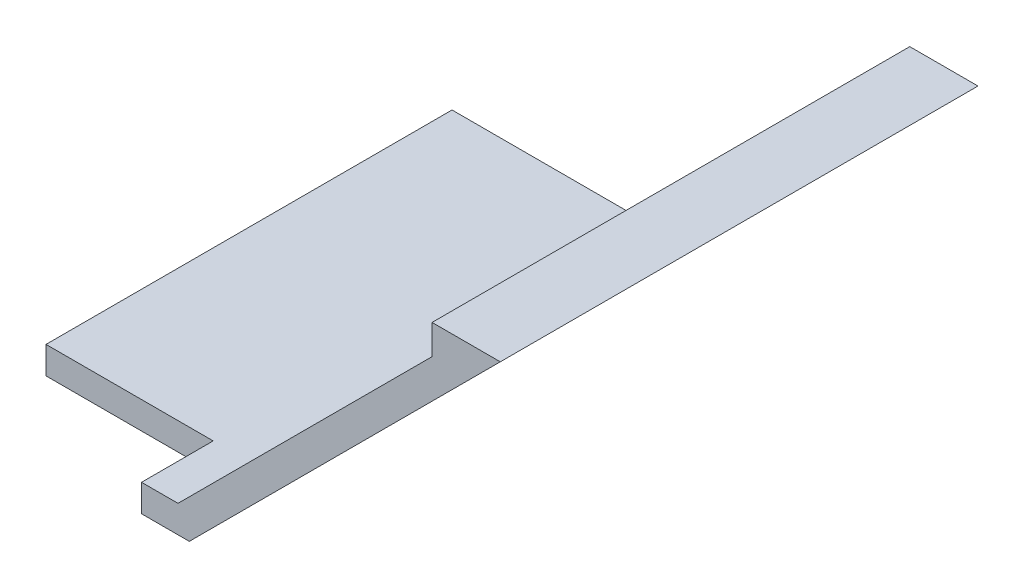
SolidWorks part; units mm, degrees
ref_plane "Plan de face" through (0, 0, 0) normal (0, 0, 1) x (1, 0, 0)
ref_plane "Plan de dessus" through (0, 0, 0) normal (0, 1, 0) x (1, 0, 0)
ref_plane "Plan de droite" through (0, 0, 0) normal (1, 0, 0) x (0, 0, -1)
sketch "Main-Sketch" plane through (0, 0, 0) normal (0, 0, 1) x (1, 0, 0)
  line L0 (0, 0) -> (63, 0)
  line L1 (63, 0) -> (154.15, 91.15)
  line L2 (154.15, 91.15) -> (134.15, 91.15)
  line L3 (134.15, 91.15) -> (134.15, 82.4637)
  line L4 (134.15, 82.4637) -> (59.6863, 8)
  line L5 (59.6863, 8) -> (0, 8)
  line L6 (0, 8) -> (0, 0)
  dimension "D1" = 8
  dimension "D2" = 8
  dimension "D3" = 20
  dimension "D4" = 135
  dimension "D5" = 154.15
  dimension "D6" = 63
extrude "Main-Extrusion" add sketch "Main-Sketch" along normal blind 140
sketch "Lcd-Hole-Sketch" plane through (0, 8, 0) normal (0, 1, 0) x (-1, 0, 0)
  line L1 (0, 140) -> (-49, 140)
  line L2 (0, 140) -> (0, 119)
  line L3 (0, 119) -> (-49, 119)
  line L4 (-49, 140) -> (-49, 119)
  point P5 (0, 140)
  dimension "D1" = 21
  dimension "D2" = 49
extrude "Lcd-Hole" cut sketch "Lcd-Hole-Sketch" against normal through all
sketch "Power-Board-Hole-Sketch" plane through (22.4244, -40.5756, 188.8128) normal (0.7071, -0.7071, 0) x (0, 0, -1)
  line L1 (168.8128, 156.2882) -> (68.8128, 156.2882)
  line L2 (168.8128, 156.2882) -> (168.8128, 77.3826)
  line L3 (168.8128, 77.3826) -> (68.8128, 77.3826)
  line L4 (68.8128, 156.2882) -> (68.8128, 77.3826)
  line L6 (188.8128, 57.3826) -> (188.8128, 186.2882) construction
  line L7 (48.8128, 57.3826) -> (48.8128, 186.2882) construction
  line L8 (48.8128, 57.3826) -> (188.8128, 57.3826) construction
  line L9 (48.8128, 186.2882) -> (188.8128, 186.2882) construction
  point P4 (80.7153, 156.2882)
  point P5 (99.7549, 77.3826)
  point P12 (120, 64.5477)
  point P13 (50, 64.5477)
  dimension "D1" = 20
  dimension "D2" = 20
  dimension "D3" = 30
  dimension "D4" = 20
extrude "Power-Board-Hole" cut sketch "Power-Board-Hole-Sketch" against normal through all
sketch "Power-Board-Window-Sketch" plane through (22.4244, -40.5756, 188.8128) normal (0.7071, -0.7071, 0) x (0, 0, -1)
  line L0 (168.8128, 77.3826) -> (168.8128, 156.2882) construction
  line L1 (176.8128, 164.2882) -> (60.8128, 164.2882)
  line L2 (176.8128, 164.2882) -> (176.8128, 69.3826)
  line L3 (176.8128, 69.3826) -> (60.8128, 69.3826)
  line L4 (60.8128, 164.2882) -> (60.8128, 69.3826)
  line L5 (168.8128, 156.2882) -> (68.8128, 156.2882) construction
  line L6 (68.8128, 156.2882) -> (68.8128, 77.3826) construction
  line L7 (68.8128, 77.3826) -> (168.8128, 77.3826) construction
  dimension "D1" = 8
  dimension "D2" = 8
  dimension "D3" = 8
  dimension "D4" = 8
extrude "Power-Board-Window" cut sketch "Power-Board-Window-Sketch" against normal blind 5
